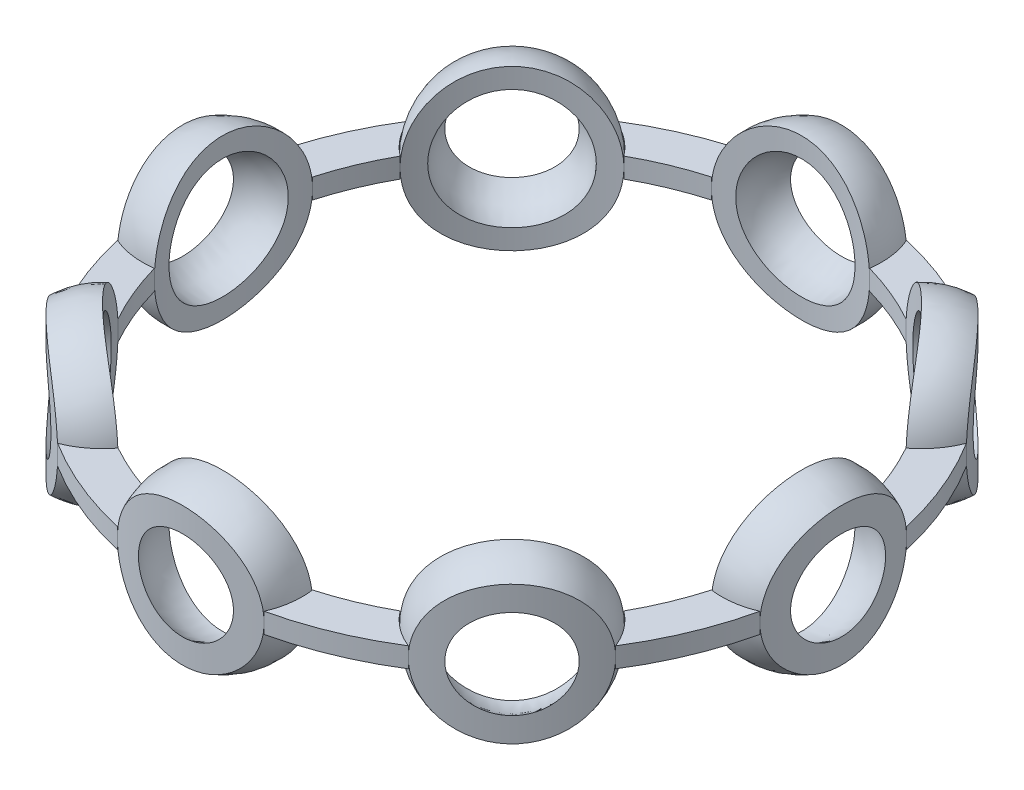
SolidWorks part; units mm, degrees
ref_plane "Front Plane" through (0, 0, 0) normal (0, 0, 1) x (1, 0, 0)
ref_plane "Top Plane" through (0, 0, 0) normal (0, 1, 0) x (1, 0, 0)
ref_plane "Right Plane" through (0, 0, 0) normal (1, 0, 0) x (0, 0, -1)
ref_plane "Plane1" through (14.5, 0, 0) normal (1, 0, 0) x (0, 0, -1)
sketch "Sketch4" plane through (14.5, 0, 0) normal (1, 0, 0) x (0, 0, -1)
  line L0 (7.4095, 0) -> (-7.4095, 0) construction
  circle A0 centre (0, 0) radius 4
  circle A1 centre (0, 0) radius 3
  point P7 (0, 0)
  dimension "D1" = 6
  dimension "D2" = 8
revolve "Revolve9" add sketch "Sketch4" angle 360 about L0 region at (14.5, 0.0894, -3.5) reverse direction yes
sketch "Sketch9" plane through (0, 0, 0) normal (1, 0, 0) x (0, 0, -1)
  line L0 (0, 4.876) -> (0, -4.876) construction
  point P4 (0, 0)
sketch "Sketch10" plane through (0, 0, 0) normal (0, 1, 0) x (1, 0, 0)
  circle A0 centre (0, 0) radius 14.5
  circle A1 centre (0, 0) radius 16.5
  circle A2 centre (0, 0) radius 27.2159
  dimension "D1" = 29
  dimension "D2" = 33
extrude "Cut-Extrude3" cut sketch "Sketch10" against normal through all both and the other way through all contours A2 A1 | A0 region at (0, 0, 0) region at (-26.4461, 0, 0)
pattern_circular "CirPattern6" count 8 over 360 about axis through (0, 4.876, 0) along (0, -1, 0) of bodies 112
sketch "Sketch12" plane through (0, 0, 0) normal (0, 1, 0) x (1, 0, 0)
  line L0 (14.5, -4.4) -> (14.5, 4.4) construction
  arc A0 (-16.0862, -3.672) -> (-13.9712, -8.7781) centre (0, 0) ccw
  arc A1 (-13.9483, -3.9618) -> (-12.6643, -7.0615) centre (0, 0) ccw
  arc A2 (16.0862, 3.672) -> (13.9483, 3.9618) centre (14.5, 0) ccw
  arc A3 (13.9712, -8.7781) -> (12.6643, -7.0615) centre (10.253, -10.253) ccw
  arc A4 (-3.9618, -13.9483) -> (-3.672, -16.0862) centre (0, -14.5) ccw
  arc A5 (-8.7781, -13.9712) -> (-7.0615, -12.6643) centre (-10.253, -10.253) ccw
  arc A6 (-16.0862, -3.672) -> (-13.9483, -3.9618) centre (-14.5, 0) ccw
  arc A7 (-13.9712, 8.7781) -> (-12.6643, 7.0615) centre (-10.253, 10.253) ccw
  arc A8 (-3.672, 16.0862) -> (-3.9618, 13.9483) centre (0, 14.5) ccw
  arc A9 (8.7781, 13.9712) -> (7.0615, 12.6643) centre (10.253, 10.253) ccw
  arc A10 (-13.9483, 3.9618) -> (-16.0862, 3.672) centre (-14.5, 0) ccw
  arc A11 (-13.9712, 8.7781) -> (-16.0862, 3.672) centre (0, 0) ccw
  arc A12 (-12.6643, 7.0615) -> (-13.9483, 3.9618) centre (0, 0) ccw
  arc A13 (-7.0615, 12.6643) -> (-8.7781, 13.9712) centre (-10.253, 10.253) ccw
  arc A14 (-3.672, 16.0862) -> (-8.7781, 13.9712) centre (0, 0) ccw
  arc A15 (-3.9618, 13.9483) -> (-7.0615, 12.6643) centre (0, 0) ccw
  arc A16 (3.9618, 13.9483) -> (3.672, 16.0862) centre (0, 14.5) ccw
  arc A17 (8.7781, 13.9712) -> (3.672, 16.0862) centre (0, 0) ccw
  arc A18 (7.0615, 12.6643) -> (3.9618, 13.9483) centre (0, 0) ccw
  arc A19 (12.6643, 7.0615) -> (13.9712, 8.7781) centre (10.253, 10.253) ccw
  arc A20 (13.9483, 3.9618) -> (12.6643, 7.0615) centre (0, 0) ccw
  arc A21 (13.9483, -3.9618) -> (16.0862, -3.672) centre (14.5, 0) ccw
  arc A22 (13.9712, -8.7781) -> (16.0862, -3.672) centre (0, 0) ccw
  arc A23 (12.6643, -7.0615) -> (13.9483, -3.9618) centre (0, 0) ccw
  arc A24 (7.0615, -12.6643) -> (8.7781, -13.9712) centre (10.253, -10.253) ccw
  arc A25 (3.9618, -13.9483) -> (7.0615, -12.6643) centre (0, 0) ccw
  arc A26 (3.672, -16.0862) -> (8.7781, -13.9712) centre (0, 0) ccw
  arc A27 (3.672, -16.0862) -> (3.9618, -13.9483) centre (0, -14.5) ccw
  arc A28 (-8.7781, -13.9712) -> (-3.672, -16.0862) centre (0, 0) ccw
  arc A29 (-7.0615, -12.6643) -> (-3.9618, -13.9483) centre (0, 0) ccw
  arc A30 (-12.6643, -7.0615) -> (-13.9712, -8.7781) centre (-10.253, -10.253) ccw
  arc A31 (16.0862, 3.672) -> (13.9712, 8.7781) centre (0, 0) ccw
  point P25 (0, 0)
  dimension "D1" = 29
  dimension "D2" = 33
  dimension "D3" = 8
  dimension "D4" = 8
extrude "Boss-Extrude2" add sketch "Sketch12" along normal mid plane 1 separate body
